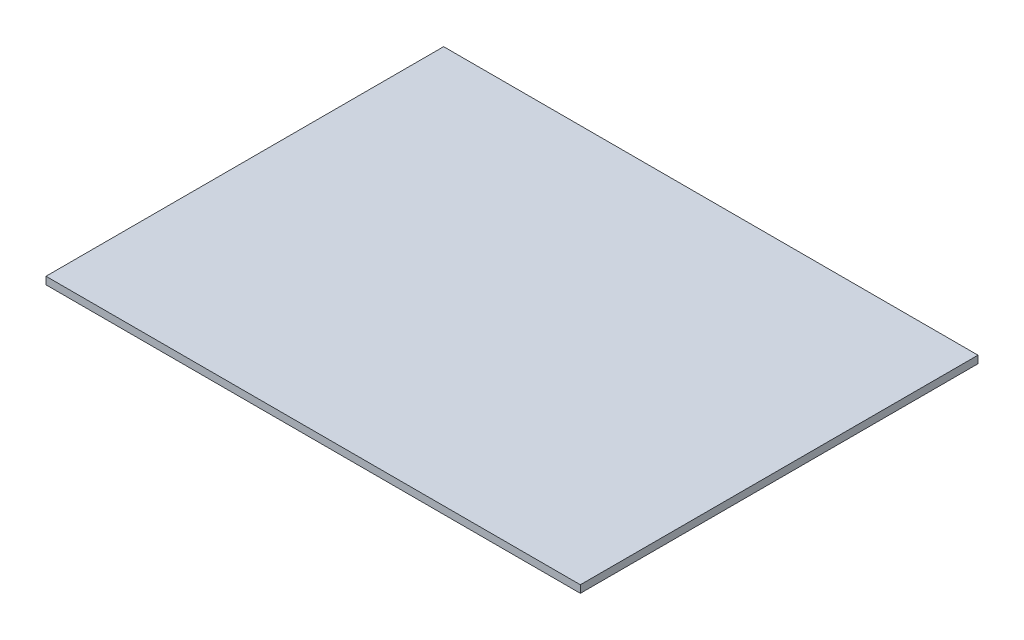
SolidWorks part; units mm, degrees
ref_plane "Front Plane" through (0, 0, 0) normal (0, 0, 1) x (1, 0, 0)
ref_plane "Top Plane" through (0, 0, 0) normal (0, 1, 0) x (1, 0, 0)
ref_plane "Right Plane" through (0, 0, 0) normal (1, 0, 0) x (0, 0, -1)
sketch "Sketch1" plane through (0, 210, 0) normal (0, 1, 0) x (1, 0, 0)
  line L0 (-107.5, 102.5) -> (-107.5, -102.5) construction
  line L1 (-107.5, 80) -> (107.5, 80)
  line L2 (-107.5, 80) -> (-107.5, -80)
  line L3 (-107.5, -80) -> (107.5, -80)
  line L4 (107.5, 80) -> (107.5, -80)
  line L5 (107.5, 122.5) -> (107.5, -227.5) construction
  line L6 (107.5, 102.5) -> (107.5, -102.5) construction
  line L7 (-107.5, 80) -> (-107.5, 102.5) construction
  line L8 (-107.5, -80) -> (-107.5, -102.5) construction
  dimension "D1" = 160
extrude "Boss-Extrude1" add sketch "Sketch1" along normal blind 3
